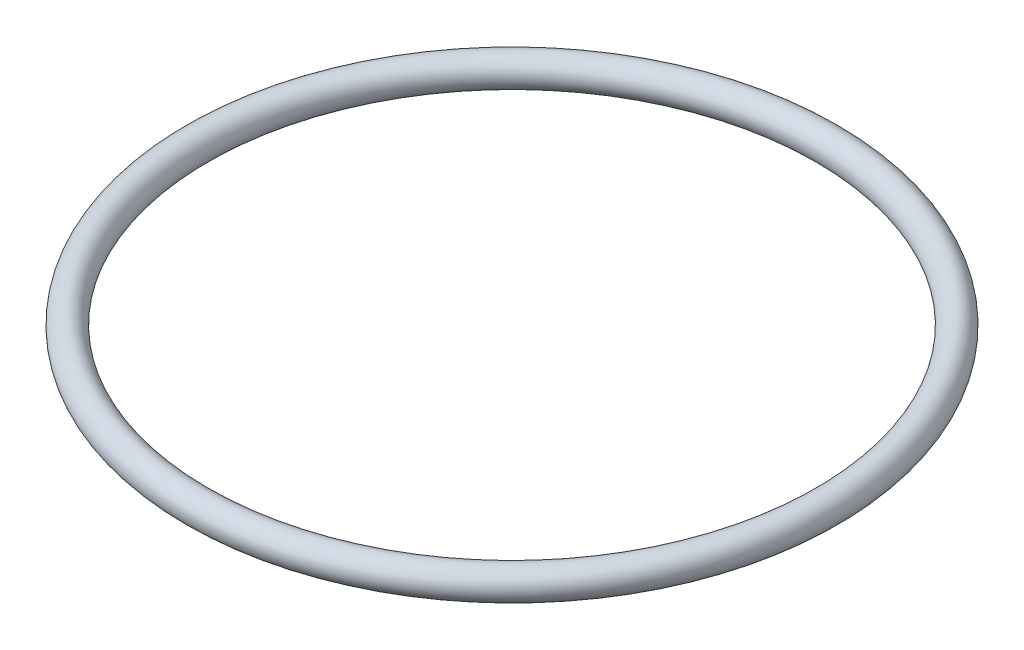
SolidWorks part; units mm, degrees
ref_plane "Alzado" through (0, 0, 0) normal (0, 0, 1) x (1, 0, 0)
ref_plane "Planta" through (0, 0, 0) normal (0, 1, 0) x (1, 0, 0)
ref_plane "Vista lateral" through (0, 0, 0) normal (1, 0, 0) x (0, 0, -1)
sketch "Croquis1" plane through (0, 0, 0) normal (1, 0, 0) x (0, 0, -1)
  line L0 (-27.345, 6.3614) -> (-27.345, -6.7584) construction
  circle A0 centre (0, 0) radius 1.31
  dimension "D1" = 2.62
  dimension "D2" = 27.345
revolve "Revolución1" add sketch "Croquis1" angle 360 about L0
sketch "Croquis2" plane through (0, 0, 0) normal (1, 0, 0) x (0, 0, -1)
  line L0 (-27.345, 21.6843) -> (-27.345, -21.6168) construction
  dimension "D1" = 27.345
ref_plane "Plane1" through (0, 0, 27.35) normal (0, 0, 1) x (1, 0, 0)
ref_axis "Axis1" through (0, 7.8273, 27.35) along (0, -1, 0)
ref_plane "Plane2" through (0, 1.31, 0) normal (0, 1, 0) x (1, 0, 0)
